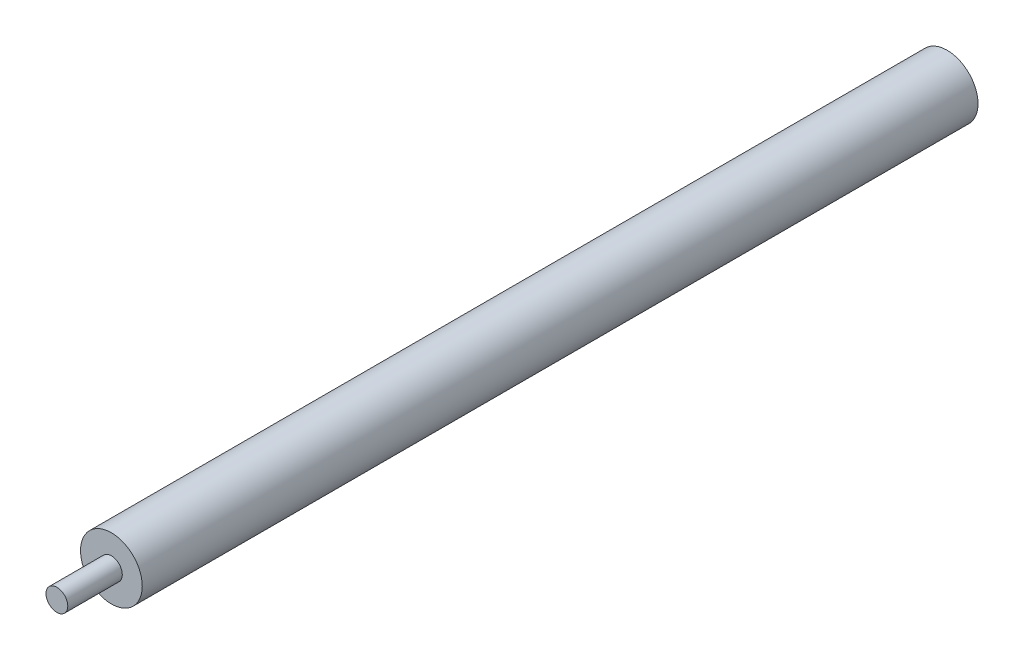
SolidWorks part; units mm, degrees
material "4032-T6"
ref_plane "Front Plane" through (0, 0, 0) normal (0, 0, 1) x (1, 0, 0)
ref_plane "Top Plane" through (0, 0, 0) normal (0, 1, 0) x (1, 0, 0)
ref_plane "Right Plane" through (0, 0, 0) normal (1, 0, 0) x (0, 0, -1)
sketch "Sketch1" plane through (0, 0, 0) normal (0, 0, 1) x (1, 0, 0)
  circle A0 centre (0, 0) radius 8.5
  dimension "D1" = 17
extrude "Boss-Extrude1" add sketch "Sketch1" along normal blind 230
sketch "Sketch2" plane through (0, 0, 230) normal (0, 0, 1) x (1, 0, 0)
  circle A0 centre (0, 0) radius 3
extrude "Boss-Extrude2" add sketch "Sketch2" along normal blind 15
